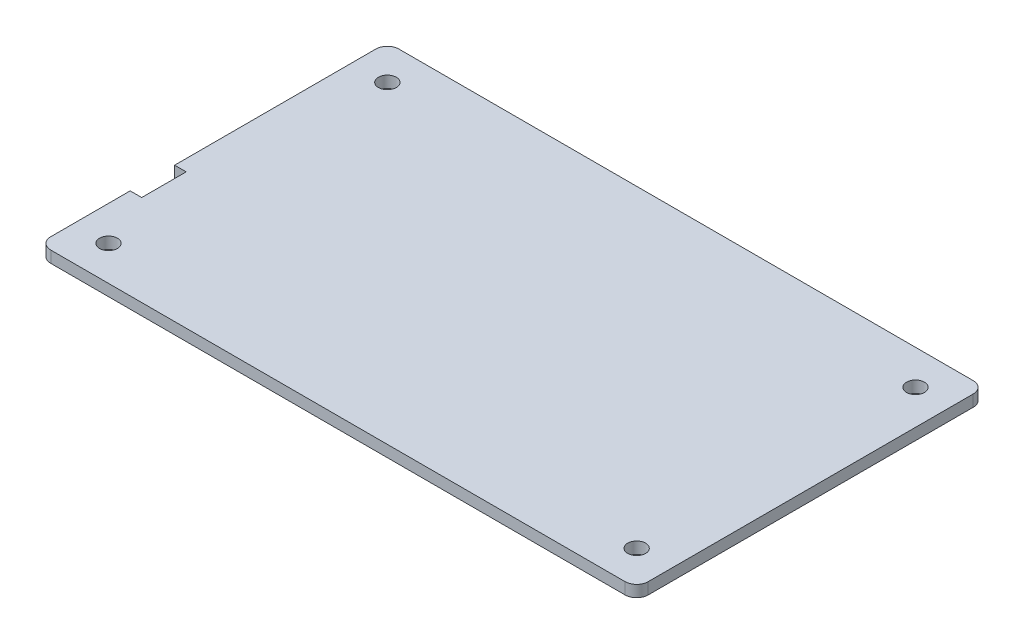
SolidWorks part; units mm, degrees
ref_plane "前视基准面" through (0, 0, 0) normal (0, 0, 1) x (1, 0, 0)
ref_plane "上视基准面" through (0, 0, 0) normal (0, 1, 0) x (1, 0, 0)
ref_plane "右视基准面" through (0, 0, 0) normal (1, 0, 0) x (0, 0, -1)
sketch "草图1" plane through (0, 0, 0) normal (0, 1, 0) x (1, 0, 0)
  line L0 (0, 0) -> (-12.7865, 0) construction
  line L1 (0, 0) -> (0, 22.3168) construction
  line L2 (91.46, 0) -> (91.46, 15.7584) construction
  line L3 (91.46, 48.29) -> (79.4981, 48.29) construction
  line L4 (-6, 0) -> (-6, 22.3168) construction
  line L5 (0, -6) -> (-12.7865, -6) construction
  line L6 (91.46, 54.29) -> (79.4981, 54.29) construction
  line L7 (97.46, 0) -> (97.46, 15.7584) construction
  line L8 (95.46, 54.29) -> (-4, 54.29)
  line L9 (-6, 52.29) -> (-6, -4)
  line L10 (-4, -6) -> (95.46, -6)
  line L11 (97.46, -4) -> (97.46, 52.29)
  line L12 (0, 9.75) -> (-12.7865, 9.75) construction
  line L13 (0, 17.45) -> (-12.7865, 17.45) construction
  line L14 (-4, 52.29) -> (-4, -4) construction
  line L16 (-6, 17.45) -> (-4, 17.45)
  line L17 (-6, 17.45) -> (-6, 9.75)
  line L18 (-6, 9.75) -> (-4, 9.75)
  line L19 (-4, 17.45) -> (-4, 9.75)
  circle A0 centre (0, 0) radius 1.55
  circle A1 centre (91.46, 0) radius 1.55
  circle A2 centre (91.46, 48.29) radius 1.55
  circle A3 centre (0, 48.29) radius 1.55
  circle A4 centre (-4, 52.29) radius 2
  circle A5 centre (-4, -4) radius 2
  circle A6 centre (95.46, -4) radius 2
  circle A7 centre (95.46, 52.29) radius 2
  dimension "D1" = 2
  dimension "D9" = 2
  dimension "D7" = 15.75
  dimension "D8" = 7.7
  dimension "D3" = 6
  dimension "D4" = 6
  dimension "D5" = 6
  dimension "D6" = 6
  dimension "D2" = 2
extrude "凸台-拉伸1" add sketch "草图1" along normal blind 2 contours A7 L8 A4 L9 A5 L10 A6 L11 A3 A2 A1 A0 | A5 | A4 | A7 | A6 region at (45.8573, 0, -24.1715) region at (95.46, 0, -52.29) region at (-4, 0, -52.29) region at (95.46, 0, 4) region at (-4, 0, 4)
